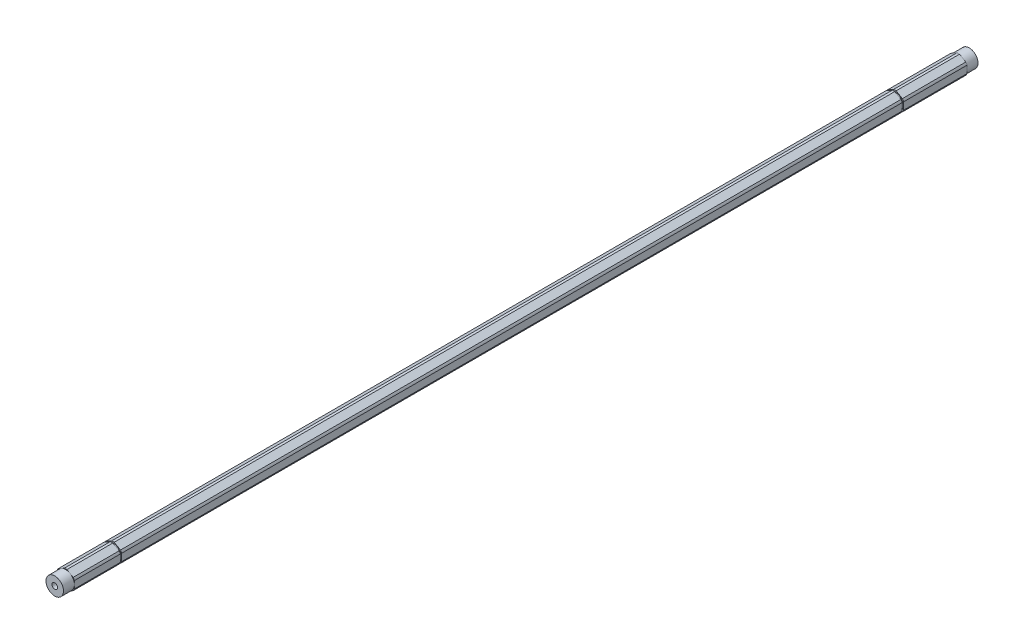
SolidWorks part; units mm, degrees
material "7075-T6 (SN)"
ref_plane "Front Plane" through (0, 0, 0) normal (0, 0, 1) x (1, 0, 0)
ref_plane "Top Plane" through (0, 0, 0) normal (0, 1, 0) x (1, 0, 0)
ref_plane "Right Plane" through (0, 0, 0) normal (1, 0, 0) x (0, 0, -1)
sketch "Sketch1" plane through (0, 0, 0) normal (0, 0, 1) x (1, 0, 0)
  line L1 (0, 7.3323) -> (-6.35, 3.6662)
  line L2 (-6.35, 3.6662) -> (-6.35, -3.6662)
  line L3 (-6.35, -3.6662) -> (0, -7.3323)
  line L4 (0, -7.3323) -> (6.35, -3.6662)
  line L5 (6.35, -3.6662) -> (6.35, 3.6662)
  line L6 (6.35, 3.6662) -> (0, 7.3323)
  circle A0 centre (0, 0) radius 6.35 construction
  circle A1 centre (0, 0) radius 2.0193
  circle A2 centre (0, 0) radius 6.875
  dimension "D1" = 12.7
  dimension "D2" = 4.0386
  dimension "D3" = 13.75
extrude "Boss-Extrude1" add sketch "Sketch1" along normal mid plane 663.575 contours L5 A2 L6 L1 L2 L3 L4 A1 region at (0, 6.6878, 0)
sketch "Sketch2" plane through (0, 0, -331.7875) normal (0, 0, -1) x (-1, 0, 0)
  circle A0 centre (0, 0) radius 6.35
  dimension "D1" = 12.7
extrude "Cut-Extrude-Thin1" cut sketch "Sketch2" against normal blind 7.9375 thin thin type one direction wall 2.54
sketch "Sketch3" plane through (0, 0, 0) normal (0, 1, 0) x (1, 0, 0)
  line L0 (8.1546, -289.5219) -> (5.9436, -289.5219)
  line L1 (8.6172, 277.8125) -> (5.9436, 277.8125)
  line L2 (8.6172, 277.8125) -> (8.6172, 276.8219)
  line L3 (8.6172, 276.8219) -> (5.9436, 276.8219)
  line L4 (5.9436, 277.8125) -> (5.9436, 276.8219)
  line L5 (8.1546, -289.5219) -> (8.1546, -290.5125)
  line L6 (8.1546, -290.5125) -> (5.9436, -290.5125)
  line L7 (5.9436, -289.5219) -> (5.9436, -290.5125)
  line L8 (5.457, -331.7875) -> (0.893, -331.7875) construction
  line L9 (6.35, 331.7875) -> (-6.35, 331.7875) construction
  line L11 (0, -331.7875) -> (0, 323.85) construction
  dimension "D1" = 0.9906
  dimension "D2" = 53.975
  dimension "D3" = 5.9436
  dimension "D5" = 41.275
revolve "Cut-Revolve4" cut sketch "Sketch3" angle 360 about axis through (0, 0, -323.85) along (0, 0, -1)
mirror "Mirror1" about plane through (0, 0, 0) normal (0, 0, 1) of "Cut-Extrude-Thin1"
hole_wizard "#10-32 Tapped Hole1" positions "3DSketch1" profile "Sketch4" tap size "#10-32" standard "ANSI Inch"
sketch3d "3DSketch1"
  circle A0 centre (0, 0, 331.7875) radius 2.0193 construction
  circle A1 centre (0, 0, -331.7875) radius 2.0193 construction
  point P0 (0, 0, -331.7875)
  point P2 (0, 0, 331.7875)
  point P8 (0, 0, 333.8068)
  point P12 (0, 0, -329.7682)
sketch "Sketch4" plane through (0, 0, -331.7875) normal (1, 0, 0) x (0, 1, 0)
  line L0 (0, 0) -> (0, 13.2428)
  line L1 (0, 13.2428) -> (2.0193, 12.0294)
  line L2 (2.0193, 12.0294) -> (2.0193, 0)
  line L5 (2.0193, 0) -> (0, 0)
  line L10 (0, 13.2428) -> (-2.0193, 12.0294) construction
  line L11 (0, -6.35) -> (0, 107.95) construction
  dimension "Tap Drill Dia." = 4.0386
  dimension "Tap Drill Depth" = 12.0294
  dimension "Drill Angle" = 118
cosmetic thread "Hole Thread1" parameters "D1"=9.652, "D2"=4.826
cosmetic thread "Hole Thread2" parameters "D1"=9.652, "D2"=4.826
equation "\"D3@Sketch1\"=13.75mm"
